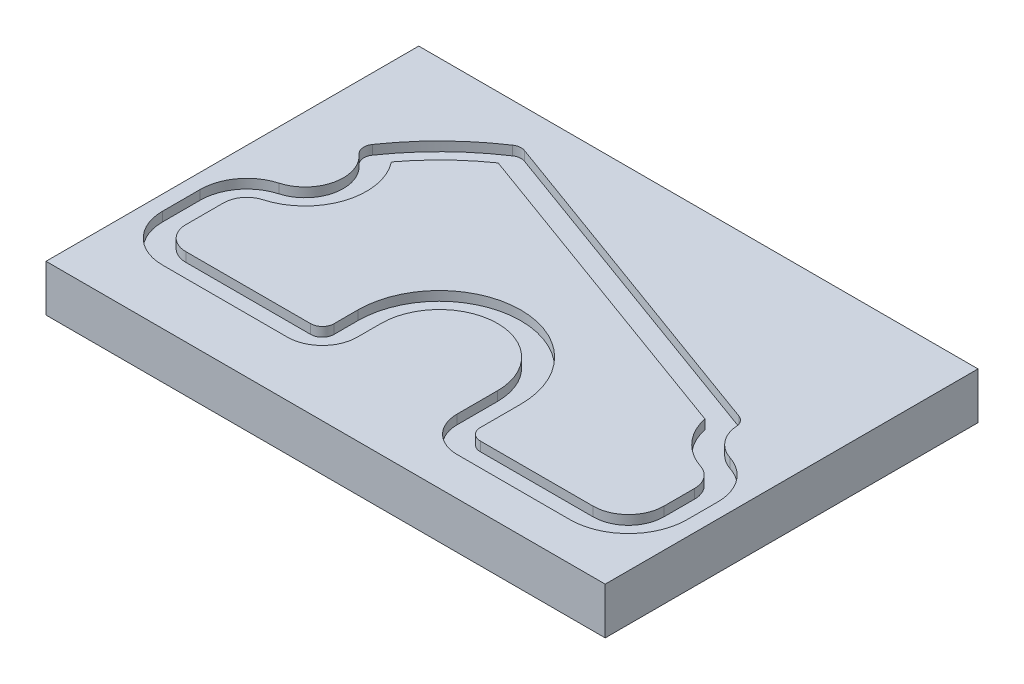
SolidWorks part; units mm, degrees
ref_plane "Front Plane" through (0, 0, 0) normal (0, 0, 1) x (1, 0, 0)
ref_plane "Top Plane" through (0, 0, 0) normal (0, 1, 0) x (1, 0, 0)
ref_plane "Right Plane" through (0, 0, 0) normal (1, 0, 0) x (0, 0, -1)
sketch "Sketch1" plane through (0, 0, 0) normal (0, 1, 0) x (1, 0, 0)
  line L0 (-59.436, -9.652) -> (-25.4, -9.652)
  line L1 (-22.225, -6.477) -> (-22.225, 0)
  line L2 (22.225, 0) -> (22.225, -11.049)
  line L3 (25.4, -14.224) -> (56.134, -14.224)
  line L4 (65.786, -4.572) -> (65.786, 3.7863)
  line L5 (-37.8039, 53.8392) -> (50.8, 21.59)
  line L6 (-65.786, -3.302) -> (-65.786, 6.9854)
  arc A0 (-22.225, 0) -> (22.225, 0) centre (0, 0) cw
  arc A1 (50.8, 21.59) -> (61.3983, 9.8255) centre (66.294, 24.892) ccw
  arc A2 (-61.1805, 13.091) -> (-52.5801, 39.5365) centre (-65.786, 29.21) ccw
  arc A3 (-37.8039, 53.8392) -> (-52.5801, 39.5365) centre (0, 0) ccw
  arc A4 (22.225, -11.049) -> (25.4, -14.224) centre (25.4, -11.049) ccw
  arc A5 (-25.4, -9.652) -> (-22.225, -6.477) centre (-25.4, -6.477) ccw
  arc A6 (56.134, -14.224) -> (65.786, -4.572) centre (56.134, -4.572) ccw
  arc A7 (-59.436, -9.652) -> (-65.786, -3.302) centre (-59.436, -3.302) cw
  arc A8 (-65.786, 6.9854) -> (-61.1805, 13.091) centre (-59.436, 6.9854) cw
  arc A9 (65.786, 3.7863) -> (61.3983, 9.8255) centre (59.436, 3.7863) ccw
  dimension "D1" = 3.175
  dimension "D2" = 9.652
  dimension "D3" = 6.35
extrude "Boss-Extrude1" add sketch "Sketch1" along normal blind 2.54
sketch "Sketch2" plane through (0, 0, 0) normal (0, -1, 0) x (1, 0, 0)
  line L1 (-76.2, 30.988) -> (-76.2, -70.6002)
  line L2 (76.2, 30.988) -> (76.2, -70.612)
  line L3 (-76.2, -70.6002) -> (76.2, -70.612)
  line L4 (-76.2, 30.988) -> (76.2, 30.988)
  point P0 (-76.2, 31.75)
  point P1 (-76.2, -69.85)
  point P2 (76.2, 31.75)
  point P3 (76.2, -69.85)
  point P8 (-88.9, -57.15)
  point P9 (88.9, -57.15)
  point P10 (-88.9, 19.05)
  point P11 (88.9, 19.05)
  point P18 (76.2, 20.0127)
  dimension "D1" = 30.988
  dimension "D3" = 16.764
  dimension "6." = 152.4
extrude "Boss-Extrude2" add sketch "Sketch2" along normal blind 10.16
sketch "Sketch9" plane through (0, 2.54, 0) normal (0, 1, 0) x (1, 0, 0)
  line L97 (76.2, -30.988) -> (76.2, 70.612)
  line L98 (15.875, 0) -> (15.875, -11.049)
  line L99 (25.4, -20.574) -> (56.134, -20.574)
  line L100 (72.136, -4.572) -> (72.136, 3.7863)
  line L101 (56.8835, 26.1333) -> (-38.6533, 60.9059)
  line L102 (-72.136, 6.9854) -> (-72.136, -3.302)
  line L103 (-59.436, -16.002) -> (-25.4, -16.002)
  line L104 (-15.875, -6.477) -> (-15.875, 0)
  line L105 (15.875, 0) -> (15.875, -11.049)
  line L106 (25.4, -20.574) -> (56.134, -20.574)
  line L107 (72.136, -4.572) -> (72.136, 3.7863)
  line L108 (56.8835, 26.1333) -> (-38.6533, 60.9059)
  line L109 (-72.136, 6.9854) -> (-72.136, -3.302)
  line L110 (-59.436, -16.002) -> (-25.4, -16.002)
  line L111 (-15.875, -6.477) -> (-15.875, 0)
  line L112 (-76.2, -30.988) -> (76.2, -30.988)
  line L113 (-76.2, 70.6002) -> (-76.2, -30.988)
  line L114 (76.2, 70.612) -> (-76.2, 70.6002)
  line L115 (76.2, -30.988) -> (76.2, 70.612)
  line L116 (-76.2, -30.988) -> (76.2, -30.988)
  line L117 (-76.2, 70.6002) -> (-76.2, -30.988)
  line L118 (76.2, 70.612) -> (-76.2, 70.6002)
  arc A33 (15.875, 0) -> (-15.875, 0) centre (0, 0) ccw
  arc A34 (15.875, 0) -> (-15.875, 0) centre (0, 0) ccw
  arc A138 (15.875, 0) -> (-15.875, 0) centre (0, 0) ccw
  arc A139 (15.875, -11.049) -> (25.4, -20.574) centre (25.4, -11.049) ccw
  arc A140 (56.134, -20.574) -> (72.136, -4.572) centre (56.134, -4.572) ccw
  arc A141 (72.136, 3.7863) -> (63.3607, 15.8646) centre (59.436, 3.7863) ccw
  arc A142 (56.8835, 26.1333) -> (63.3607, 15.8646) centre (66.294, 24.892) ccw
  arc A143 (-38.6533, 60.9059) -> (-61.0217, 38.4703) centre (0, 0) ccw
  arc A144 (-62.925, 19.1967) -> (-61.0217, 38.4703) centre (-65.786, 29.21) ccw
  arc A145 (-62.925, 19.1967) -> (-72.136, 6.9854) centre (-59.436, 6.9854) ccw
  arc A146 (-72.136, -3.302) -> (-59.436, -16.002) centre (-59.436, -3.302) ccw
  arc A147 (-25.4, -16.002) -> (-15.875, -6.477) centre (-25.4, -6.477) ccw
  arc A149 (15.875, -11.049) -> (25.4, -20.574) centre (25.4, -11.049) ccw
  arc A150 (56.134, -20.574) -> (72.136, -4.572) centre (56.134, -4.572) ccw
  arc A151 (72.136, 3.7863) -> (63.3607, 15.8646) centre (59.436, 3.7863) ccw
  arc A152 (56.8835, 26.1333) -> (63.3607, 15.8646) centre (66.294, 24.892) ccw
  arc A153 (-38.6533, 60.9059) -> (-61.0217, 38.4703) centre (0, 0) ccw
  arc A154 (-62.925, 19.1967) -> (-61.0217, 38.4703) centre (-65.786, 29.21) ccw
  arc A155 (-62.925, 19.1967) -> (-72.136, 6.9854) centre (-59.436, 6.9854) ccw
  arc A156 (-72.136, -3.302) -> (-59.436, -16.002) centre (-59.436, -3.302) ccw
  arc A157 (-25.4, -16.002) -> (-15.875, -6.477) centre (-25.4, -6.477) ccw
  dimension "D1" = 6.35
  dimension "D2" = 0
  dimension "D3" = 6.35
extrude "Boss-Extrude4" add sketch "Sketch9" against normal blind 2.54
fillet "Fillet1" radius 3.175 1 edges at (-38.6533, 1.27, -60.9059)
fillet "Fillet2" radius 3.175 1 edges at (56.8835, 1.27, -26.1333)
fillet "Fillet3" radius 3.175 1 edges at (-61.0217, 1.27, -38.4703)
